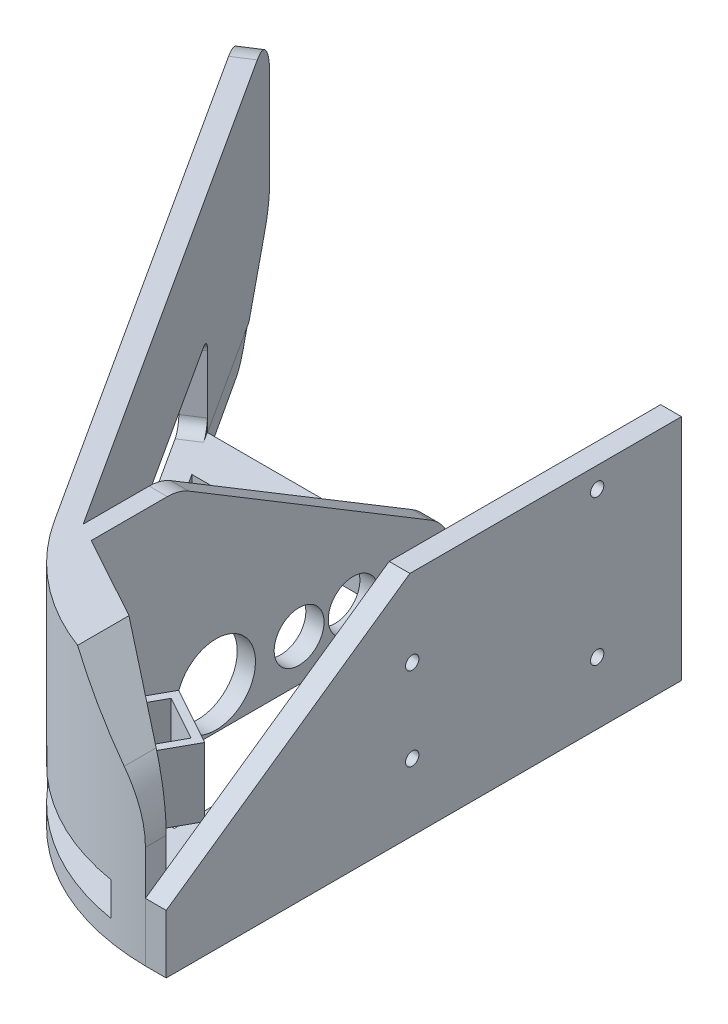
SolidWorks part; units mm, degrees
ref_plane "Front Plane" through (0, 0, 0) normal (0, 0, 1) x (1, 0, 0)
ref_plane "Top Plane" through (0, 0, 0) normal (0, 1, 0) x (1, 0, 0)
ref_plane "Right Plane" through (0, 0, 0) normal (1, 0, 0) x (0, 0, -1)
sketch "Sketch1" plane through (0, 0, 0) normal (0, 1, 0) x (1, 0, 0)
  line L0 (-48.7821, 26.8903) -> (-130, 153)
  line L1 (0, 0) -> (155, 0)
  line L2 (0, 0) -> (0, 5)
  line L3 (0, 5) -> (155, 5)
  line L4 (155, 0) -> (155, 5)
  line L5 (-130, 153) -> (-125.7963, 155.7073)
  line L6 (-125.7963, 155.7073) -> (-44.5785, 29.5976)
  line L7 (-44.5785, 29.5976) -> (-48.7821, 26.8903)
  line L8 (-44.5785, 29.5976) -> (0, 5)
  line L9 (-44.5785, 29.5976) -> (-48.7821, 26.8903)
  line L10 (0, 5) -> (0, 0)
  arc A0 (0, 0) -> (-48.7821, 26.8903) centre (0.3966, 58.4127) cw
  dimension "D1" = 130
  dimension "D3" = 150
  dimension "D4" = 58.4141
  dimension "D2" = 153
  dimension "D5" = 90
  dimension "D6" = 0
  dimension "D7" = 150
  dimension "D8" = 155
  dimension "D9" = 5
  dimension "D10" = 5
extrude "Boss-Extrude2" add sketch "Sketch1" along normal blind 55 contours L7 L6 L5 L0 | A0 L2 L8 L7 | L1 L4 L3 L2
sketch "Sketch2" plane through (0, 0, 0) normal (0, 0, 1) x (1, 0, 0)
  line L0 (0, 0) -> (155, 0) construction
  line L1 (155, 55) -> (43, 55)
  line L2 (155, 55) -> (155, 10)
  line L3 (155, 10) -> (43, 10)
  line L4 (43, 55) -> (43, 10)
  line L5 (5, 50) -> (35, 50)
  line L6 (5, 50) -> (5, 25)
  line L7 (5, 25) -> (35, 25)
  line L8 (35, 50) -> (35, 25)
  line L9 (0, 55) -> (0, 0) construction
  circle A0 centre (5, 50) radius 1.75
  circle A1 centre (35, 50) radius 1.75
  circle A2 centre (5, 25) radius 1.75
  circle A3 centre (35, 25) radius 1.75
  line M10 (155, 0) -> (155, 55)
  line M11 (155, 55) -> (0, 55)
  dimension "D6" = 3.5
  dimension "D7" = 3.5
  dimension "D8" = 3.5
  dimension "D9" = 3.5
  dimension "D2" = 25
  dimension "D3" = 25
  dimension "D4" = 30
  dimension "D5" = 5
  dimension "D10" = 10
  dimension "D11" = 8
  dimension "D12" = 8
extrude "Cut-Extrude1" cut sketch "Sketch2" against normal blind 55 contours L4 L3 M11 M10 | A2 | A0 | A1 | A3
sketch "Sketch3" plane through (-22.2397, 0, 14.3229) normal (-0.8407, 0, 0.5415) x (0.5415, 0, 0.8407)
  line L0 (-49.0207, 55) -> (-49.0207, 0) construction
  line L1 (-49.0207, 25) -> (-149.0207, 25)
  line L2 (-49.0207, 25) -> (-49.0207, 5)
  line L3 (-49.0207, 5) -> (-149.0207, 5)
  line L4 (-149.0207, 25) -> (-149.0207, 5)
  line L5 (-49.0207, 0) -> (-199.0207, 0) construction
  dimension "D1" = 5
  dimension "D2" = 20
  dimension "D3" = 100
extrude "Cut-Extrude2" cut sketch "Sketch3" against normal blind 55
sketch "Sketch4" plane through (2.115, 0, -3.833) normal (0.4831, 0, -0.8756) x (-0.8756, 0, -0.4831)
  line L6 (53.33, 25) -> (53.33, 5) construction
  line L11 (53.33, 0) -> (2.4156, 0) construction
  line L12 (8.33, 13.0659) -> (48.33, 13.0659)
  line L13 (8.33, 13.0659) -> (8.33, 5)
  line L14 (8.33, 5) -> (48.33, 5)
  line L15 (48.33, 13.0659) -> (48.33, 5)
  dimension "D1" = 5
  dimension "D2" = 40
  dimension "D3" = 5
extrude "Cut-Extrude3" cut sketch "Sketch4" against normal blind 55
sketch "Sketch5" plane through (0, 0, 0) normal (0, -1, 0) x (1, 0, 0)
  line L0 (0, -5) -> (-44.5785, -29.5976)
  line L2 (0, -5) -> (0, -155.7073)
  line L3 (0, -155.7073) -> (-125.7963, -155.7073)
  line L5 (-44.5785, -29.5976) -> (0, -5) construction
  line L6 (-44.5785, -29.5976) -> (-125.7963, -155.7073)
extrude "Boss-Extrude4" add sketch "Sketch5" against normal blind 5
sketch "Sketch8" plane through (0, 5, 0) normal (0, 1, 0) x (1, 0, 0)
  line L5 (-44.5785, 29.5976) -> (-98.7237, 113.6707)
  line L7 (-44.5785, 29.5976) -> (-44.5785, 113.6707)
  line L8 (-44.5785, 113.6707) -> (-98.7237, 113.6707)
extrude "Cut-Extrude4" cut sketch "Sketch8" against normal blind 50
sketch "Sketch9" plane through (0, 5, 0) normal (0, 1, 0) x (1, 0, 0)
  line L1 (-40.2007, 27.182) -> (-44.5785, 27.182)
  line L2 (-40.2007, 27.182) -> (-40.2007, 113.6707)
  line L3 (-40.2007, 113.6707) -> (-44.5785, 113.6707)
  line L4 (-44.5785, 27.182) -> (-44.5785, 113.6707)
extrude "Boss-Extrude7" add sketch "Sketch9" along normal blind 50
sketch "Sketch10" plane through (0, 5, 0) normal (0, 1, 0) x (1, 0, 0)
  line L1 (-40.2007, 113.6707) -> (-20.2007, 113.6707)
  line L2 (-40.2007, 113.6707) -> (-40.2007, 27.1384)
  line L3 (-40.2007, 27.1384) -> (-20.2007, 27.1384)
  line L4 (-20.2007, 113.6707) -> (-20.2007, 27.1384)
  dimension "D1" = 20
extrude "Cut-Extrude5" cut sketch "Sketch10" against normal blind 10
sketch "Sketch12" plane through (-40.2007, 0, 0) normal (1, 0, 0) x (0, 0, -1)
  line L6 (27.182, 5) -> (27.182, 13.0659) construction
  circle A0 centre (57.182, 10) radius 9.5
  circle A1 centre (77.182, 10) radius 6
  dimension "D4" = 19
  dimension "D5" = 12
  dimension "D1" = 30
  dimension "D3" = 20
extrude "Cut-Extrude6" cut sketch "Sketch12" against normal blind 10
sketch "Sketch13" plane through (-40.2007, 0, 0) normal (1, 0, 0) x (0, 0, -1)
  circle A0 centre (57.182, 10) radius 9.5
  circle A1 centre (77.182, 10) radius 6
  circle A2 centre (57.182, 10) radius 9.5 construction
  circle A3 centre (77.182, 10) radius 6 construction
  dimension "D1" = 0
  dimension "D2" = 0
  dimension "D3" = 19
  dimension "D4" = 12
extrude "Cut-Extrude7" cut sketch "Sketch13" along normal blind 50
sketch "Sketch14" plane through (0, 5, 0) normal (0, 1, 0) x (1, 0, 0)
  line L0 (0, 103.0381) -> (-91.876, 103.0381)
  line L1 (0, 155.7073) -> (-126.1063, 155.7073)
  line L2 (0, 155.7073) -> (0, 103.0381)
  line L5 (-98.7237, 113.6707) -> (-125.7963, 155.7073) construction
  line L6 (-91.876, 103.0381) -> (-126.1063, 155.7073)
extrude "Cut-Extrude8" cut sketch "Sketch14" against normal blind 50
sketch "Sketch15" plane through (-22.2397, 0, 14.3229) normal (-0.8407, 0, 0.5415) x (0.5415, 0, 0.8407)
  line L0 (-176.0359, 0) -> (-199.0207, 18.2475)
  line L1 (-199.0207, 0) -> (-176.0359, 0)
  line L2 (-199.0207, 0) -> (-199.0207, 18.2475)
extrude "Cut-Extrude9" cut sketch "Sketch15" against normal blind 50
sketch "Sketch16" plane through (-40.2007, 0, 0) normal (1, 0, 0) x (0, 0, -1)
  line L0 (113.6707, 15.4952) -> (48.2529, 55)
  line L1 (113.6707, 55) -> (113.6707, 5) construction
  line L2 (27.182, 55) -> (113.6707, 55) construction
  line L3 (48.2529, 55) -> (113.6707, 55)
  line L4 (113.6707, 55) -> (113.6707, 15.4952)
extrude "Cut-Extrude10" cut sketch "Sketch16" against normal blind 10
fillet "Fillet5" radius 3 4 edges at (-100.8476, 5, -112.3029) (-46.6803, 25, -28.2439) (-46.6803, 5, -28.2439) (-100.8255, 25, -112.3171)
sketch "Sketch18" plane through (0, 5, 0) normal (0, 1, 0) x (1, 0, 0)
  line L1 (0, 103.0381) -> (-98.7678, 103.0381)
  line L2 (0, 103.0381) -> (0, 113.6423)
  line L3 (0, 113.6423) -> (-98.7678, 113.6423)
  line L4 (-98.7678, 103.0381) -> (-98.7678, 113.6423)
extrude "Boss-Extrude8" add sketch "Sketch18" against normal blind 5
sketch "Sketch19" plane through (0, 0, 0) normal (0, -1, 0) x (1, 0, 0)
  line L0 (-97.8232, -103.0381) -> (-98.7678, -104.5048)
  line L5 (-98.7678, -104.5048) -> (-98.7678, -103.0381)
  line L6 (-98.7678, -104.5048) -> (-98.7678, -103.0381) construction
  line L7 (-98.7678, -103.0381) -> (-97.8232, -103.0381)
extrude "Cut-Extrude11" cut sketch "Sketch19" against normal blind 5 contours L0 L5 L7
sketch "Sketch20" plane through (0, 0, 0) normal (0, -1, 0) x (1, 0, 0)
  line L1 (0, -5) -> (155, -5)
  line L2 (0, -5) -> (0, -124)
  line L3 (0, -124) -> (155, -124)
  line L4 (155, -5) -> (155, -124)
  dimension "D1" = 119
  dimension "D2" = 155
extrude "Boss-Extrude9" add sketch "Sketch20" against normal blind 10
sketch "Sketch21" plane through (155, 0, 0) normal (1, 0, 0) x (0, 0, -1)
  line L1 (124, 10) -> (0, 10) construction
  line L4 (5, 10) -> (124, 10)
  line L5 (124, 10) -> (124, 7)
  line L6 (124, 7) -> (5, 10)
  line L7 (124, 10) -> (124, 0) construction
  dimension "D1" = 5
  dimension "D2" = 0
  dimension "D3" = 3
extrude "Cut-Extrude13" cut sketch "Sketch21" against normal blind 155
sketch "Sketch24" plane through (0, 0, 0) normal (0, -1, 0) x (1, 0, 0)
  line L0 (0, -124) -> (155, -124) construction
  line L1 (125, -124) -> (0, -124)
  line L2 (125, -124) -> (125, -116)
  line L3 (125, -116) -> (0, -116)
  line L4 (0, -124) -> (0, -116)
  line L5 (155, 0) -> (155, -124) construction
  line L6 (0, -5) -> (0, -124) construction
  dimension "D1" = 30
  dimension "D2" = 0
  dimension "D3" = 8
extrude "Boss-Extrude10" add sketch "Sketch24" against normal blind 95
fillet "Fillet6" radius 20 1 edges at (62.5, 7.2017, -116)
sketch "Sketch25" plane through (0, 0, -124) normal (0, 0, -1) x (-1, 0, 0)
  line L0 (-33.25, 77) -> (-33.25, 72)
  line L6 (-125, 95) -> (0, 95) construction
  line L10 (-36.75, 77) -> (-36.75, 72)
  line L11 (-73.25, 77) -> (-73.25, 72)
  line L12 (-76.75, 77) -> (-76.75, 72)
  line L14 (0, 95) -> (0, 0) construction
  arc A4 (-36.75, 77) -> (-33.25, 77) centre (-35, 77) cw
  arc A5 (-73.25, 72) -> (-76.75, 72) centre (-75, 72) cw
  arc A6 (-73.25, 77) -> (-76.75, 77) centre (-75, 77) ccw
  arc A7 (-36.75, 72) -> (-33.25, 72) centre (-35, 72) ccw
  arc A8 (-33.25, 77) -> (-36.75, 77) centre (-35, 77) ccw
  dimension "D4" = 40
  dimension "D6" = 40
  dimension "D1" = 23
  dimension "D2" = 23
  dimension "D3" = 5
  dimension "D8" = 35
  dimension "D9" = 35
sketch "Sketch26" plane through (2.115, 0, -3.833) normal (0.4831, 0, -0.8756) x (-0.8756, 0, -0.4831)
  line L0 (48.33, 13.0659) -> (8.33, 13.0659) construction
  line L1 (36.33, 13.0659) -> (20.33, 13.0659)
  line L2 (36.33, 13.0659) -> (36.33, 14.5659)
  line L3 (36.33, 14.5659) -> (20.33, 14.5659)
  line L4 (20.33, 13.0659) -> (20.33, 14.5659)
  line L5 (8.33, 13.0659) -> (8.33, 5) construction
  line L6 (48.33, 55) -> (48.33, 13.0659) construction
  dimension "D1" = 12
  dimension "D2" = 12
  dimension "D3" = 16
  dimension "D4" = 1.5
extrude "Boss-Extrude11" add sketch "Sketch26" along normal blind 12
sketch "Sketch27" plane through (0, 14.5659, 0) normal (0, 1, 0) x (1, 0, 0)
  line L0 (-15.6851, 13.6547) -> (-9.8877, 24.1614)
  line L1 (-9.8877, 24.1614) -> (-23.8966, 31.8913)
  line L2 (-23.8966, 31.8913) -> (-29.694, 21.3846)
  line L3 (-29.694, 21.3846) -> (-28.0304, 20.4667)
  line L4 (-29.694, 21.3846) -> (-15.6851, 13.6547) construction
  line L5 (-28.0304, 20.4667) -> (-23.151, 29.3098)
  line L6 (-23.151, 29.3098) -> (-12.4692, 23.4158)
  line L7 (-12.4692, 23.4158) -> (-17.3486, 14.5727)
  line L8 (-17.3486, 14.5727) -> (-15.6851, 13.6547)
  dimension "D1" = 1.9
  dimension "D2" = 1.9
  dimension "D3" = 1.9
extrude "Boss-Extrude12" add sketch "Sketch27" along normal blind 15
sketch "Sketch28" plane through (0, 14.5659, 0) normal (0, 1, 0) x (1, 0, 0)
  circle A0 centre (-20.2498, 21.9412) radius 2.5
  dimension "D1" = 5
extrude "Cut-Extrude15" cut sketch "Sketch28" against normal blind 5
extrude "Cut-Extrude17" cut sketch "Sketch25" against normal blind 35 contours L10 A7 L0 A4 | L11 A6 L12 A5
sketch "Sketch29" plane through (0, 0, 0) normal (0, 0, 1) x (1, 0, 0)
  line L1 (43, 55) -> (0, 55)
  line L6 (0, 12) -> (43, 12)
  line L7 (0, 12) -> (0, 55)
  line L8 (43, 55) -> (43, 12)
extrude "Cut-Extrude18" cut sketch "Sketch29" against normal blind 35
fillet "Fillet9" radius 10 5 edges at (-127.8982, 55, -154.3536) (-115.5221, 0, -134.985) (-127.8982, 18.2475, -154.3536) (-42.3896, 15.4952, -113.6707) (-42.3896, 55, -48.2529)
sketch "Sketch31" plane through (155, 0, 0) normal (1, 0, 0) x (0, 0, -1)
  line L0 (124, 7) -> (124, 0) construction
  line L1 (0, 0) -> (124, 0)
  line L2 (0, 0) -> (0, 12)
  line L3 (0, 12) -> (124, 12)
  line L4 (124, 0) -> (124, 12)
  dimension "D1" = 0
  dimension "D2" = 12
extrude "Boss-Extrude14" add sketch "Sketch31" against normal blind 2
sketch "Sketch32" plane through (153, 0, 0) normal (-1, 0, 0) x (0, 0, 1)
  line L0 (-124, 12) -> (0, 12) construction
  line L1 (0, 10) -> (-5, 10)
  line L2 (0, 10) -> (0, 12)
  line L3 (0, 12) -> (-5, 12)
  line L4 (-5, 10) -> (-5, 12)
  dimension "D1" = 5
  dimension "D2" = 2
extrude "Boss-Extrude15" add sketch "Sketch32" along normal blind 132
sketch "Sketch33" plane through (0, 0, 0) normal (0, 0, 1) x (1, 0, 0)
  line L0 (0, 0) -> (155, 0) construction
  line L1 (155, 12) -> (135, 12)
  line L2 (155, 12) -> (155, 0)
  line L3 (155, 0) -> (135, 0)
  line L4 (135, 12) -> (135, 0)
  dimension "D1" = 20
extrude "Cut-Extrude19" cut sketch "Sketch33" against normal blind 160
sketch "Sketch34" plane through (0, 0, 0) normal (0, 0, 1) x (1, 0, 0)
  line L0 (0, 0) -> (135, 0) construction
  line L1 (135, 12) -> (133, 12)
  line L2 (135, 12) -> (135, 0)
  line L3 (135, 0) -> (133, 0)
  line L4 (133, 12) -> (133, 0)
  dimension "D1" = 2
extrude "Boss-Extrude17" add sketch "Sketch34" against normal blind 123
sketch "Sketch36" plane through (-40.2007, 0, 0) normal (1, 0, 0) x (0, 0, -1)
  line L0 (103.0381, 0) -> (27.1384, 0) construction
  circle A0 centre (90.1949, 10) radius 6
  dimension "D1" = 12
  dimension "D2" = 10
extrude "Cut-Extrude20" cut sketch "Sketch36" against normal mid plane 80
sketch "Sketch38" plane through (125, 0, 0) normal (1, 0, 0) x (0, 0, -1)
  line L0 (95.496, 7.7186) -> (124, 7)
  line L1 (124, 7) -> (124, 95)
  line L2 (124, 95) -> (116, 95)
  line L3 (116, 95) -> (95.496, 7.7186)
extrude "Cut-Extrude21" cut sketch "Sketch38" against normal blind 25
sketch "Sketch39" plane through (0, 0, 0) normal (0, 0, 1) x (1, 0, 0)
  line L0 (0, 0) -> (135, 0) construction
  line L1 (135, 12) -> (125, 12)
  line L2 (135, 12) -> (135, 0)
  line L3 (135, 0) -> (125, 0)
  line L4 (125, 12) -> (125, 0)
  dimension "D1" = 10
extrude "Cut-Extrude22" cut sketch "Sketch39" against normal blind 165
sketch "Sketch40" plane through (0, 0, 0) normal (0, 0, 1) x (1, 0, 0)
  line L6 (0, 0) -> (125, 0) construction
  line L7 (125, 12) -> (123, 12)
  line L8 (125, 12) -> (125, 0)
  line L9 (125, 0) -> (123, 0)
  line L10 (123, 12) -> (123, 0)
  dimension "D1" = 2
extrude "Boss-Extrude18" add sketch "Sketch40" against normal blind 115
sketch "Sketch42" plane through (0, 5, 0) normal (0, 1, 0) x (1, 0, 0)
  line L4 (0, 124) -> (0, 0)
  line L5 (0, 0) -> (5, 0)
  line L9 (5, 0) -> (5, 124)
  line L10 (0, 124) -> (5, 124)
  line L11 (0, 124) -> (125, 124) construction
  line L12 (0, 0) -> (125, 0) construction
  point P6 (0, 124)
  dimension "D1" = 0
  dimension "D2" = 124
extrude "Boss-Extrude20" add sketch "Sketch42" along normal up to surface (90 mm away) up to face at (50, 95, -120)
sketch "Sketch45" plane through (5, 0, 0) normal (1, 0, 0) x (0, 0, -1)
  line L1 (5, 10) -> (95.496, 7.7186) construction
  circle A0 centre (59.2085, 36.1358) radius 1.6
  circle A1 centre (59.2085, 16.1358) radius 1.6
  circle A2 centre (103.7183, 50.0137) radius 1.6
  circle A3 centre (103.7183, 15.0137) radius 1.6
  dimension "D5" = 3.2
  dimension "D6" = 3.2
  dimension "D7" = 3.2
  dimension "D8" = 3.2
  dimension "D3" = 7.5
  dimension "D1" = 35
  dimension "D2" = 7.5
  dimension "D4" = 20
extrude "Cut-Extrude23" cut sketch "Sketch45" against normal blind 30
sketch "Sketch51" plane through (125, 0, 0) normal (1, 0, 0) x (0, 0, -1)
  line L0 (124, 7) -> (5, 12)
  line L1 (5, 12) -> (5, 14.0956)
  line L2 (5, 14.0956) -> (0, 14.0956)
  line L3 (0, 14.0956) -> (0, 7.1134)
  line L4 (0, 12) -> (0, 0) construction
  line L5 (0, 7.1134) -> (124, 7)
extrude "Boss-Extrude22" add sketch "Sketch51" against normal blind 120
sketch "Sketch52" plane through (0, 0, 0) normal (0, 0, 1) x (1, 0, 0)
  line L0 (0, 0) -> (125, 0) construction
  line L1 (125, 14.0956) -> (123, 14.0956)
  line L2 (125, 14.0956) -> (125, 0)
  line L3 (125, 0) -> (123, 0)
  line L4 (123, 14.0956) -> (123, 0)
  dimension "D1" = 2
extrude "Boss-Extrude23" add sketch "Sketch52" against normal blind 120
sketch "Sketch54" plane through (5, 0, 0) normal (1, 0, 0) x (0, 0, -1)
  line L0 (0, 14.0956) -> (116, 95)
  line L1 (116, 95) -> (0, 95)
  line L2 (0, 95) -> (0, 14.0956)
extrude "Cut-Extrude26" cut sketch "Sketch54" against normal blind 5
fillet "Fillet14" radius 10 1 edges at (100, 7.5139, -111.7693)
fillet "Fillet15" radius 5 1 edges at (124, 14.0956, -120)
fillet "Fillet16" radius 5 1 edges at (124, 7.1681, -120)
fillet "Fillet17" radius 5 1 edges at (100, 95, -120)
fillet "Fillet18" radius 1 1 edges at (5, 10.0139, -52.2693)
sketch "Sketch55" plane through (0, 0, 0) normal (0, 0, 1) x (1, 0, 0)
  line L0 (0, 0) -> (125, 0) construction
  line L1 (5, 0) -> (148.6999, 0)
  line L2 (5, 0) -> (5, 184.0163)
  line L3 (5, 184.0163) -> (148.6999, 184.0163)
  line L4 (148.6999, 0) -> (148.6999, 184.0163)
extrude "Cut-Extrude27" cut sketch "Sketch55" against normal through all
chamfer "Chamfer2" distance 20 angle 48 1 edges at (0, 55, -2.5)
fillet "Fillet19" radius 21 1 edges at (0, 32.7877, -2.5)
sketch "Sketch58" plane through (5, 0, 0) normal (1, 0, 0) x (0, 0, -1)
  line L1 (-25.9538, 55) -> (150.6896, 55)
  line L2 (-25.9538, 55) -> (-25.9538, 106.9484)
  line L3 (-25.9538, 106.9484) -> (150.6896, 106.9484)
  line L4 (150.6896, 55) -> (150.6896, 106.9484)
  point P4 (-25.9538, 57.3378)
extrude "Cut-Extrude30" cut sketch "Sketch58" against normal blind 30
